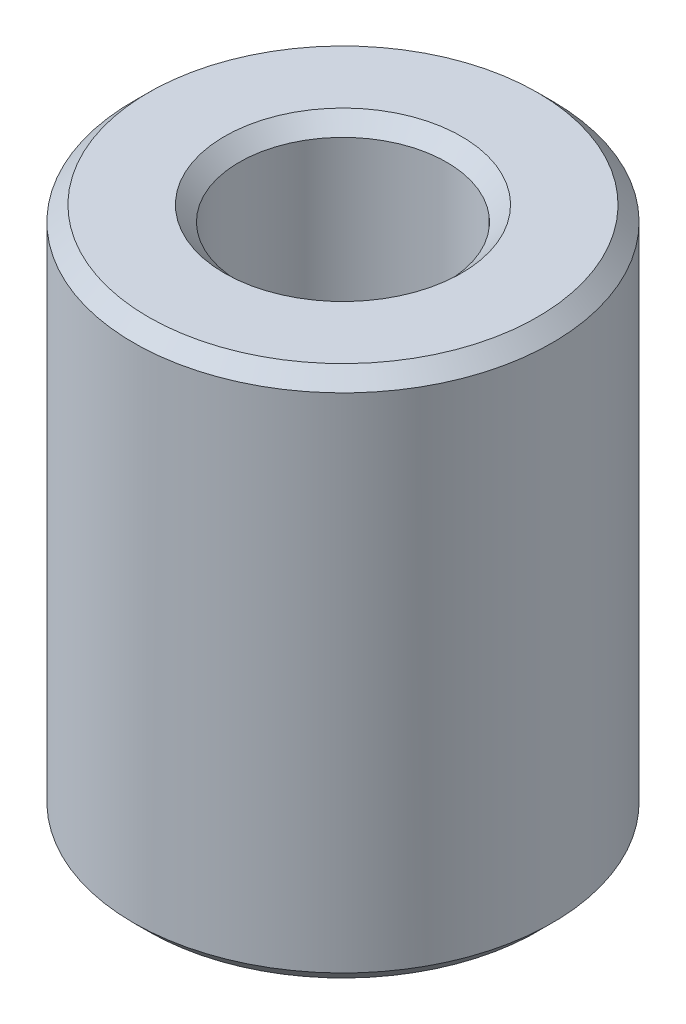
SolidWorks part; units mm, degrees
ref_plane "Front Plane" through (0, 0, 0) normal (0, 0, 1) x (1, 0, 0)
ref_plane "Top Plane" through (0, 0, 0) normal (0, 1, 0) x (1, 0, 0)
ref_plane "Right Plane" through (0, 0, 0) normal (1, 0, 0) x (0, 0, -1)
sketch "Sketch1" plane through (0, 0, 0) normal (0, 1, 0) x (1, 0, 0)
  circle A0 centre (0, 0) radius 7.5
  dimension "SLEEVE_OD" = 15
extrude "Boss-Extrude1" add sketch "Sketch1" along normal blind 19.0599
sketch "Sketch2" plane through (0, 0, 0) normal (0, 1, 0) x (1, 0, 0)
  circle A0 centre (0, 0) radius 3.7125
  dimension "BORE_D" = 7.425
extrude "Cut-Extrude1" cut sketch "Sketch2" along normal through all
chamfer "Chamfer1" distance 0.5325 angle 45 4 edges at (0, 19.0599, 3.7125) (0, 0, 3.7125) (0, 0, 7.5) (0, 19.0599, 7.5)
